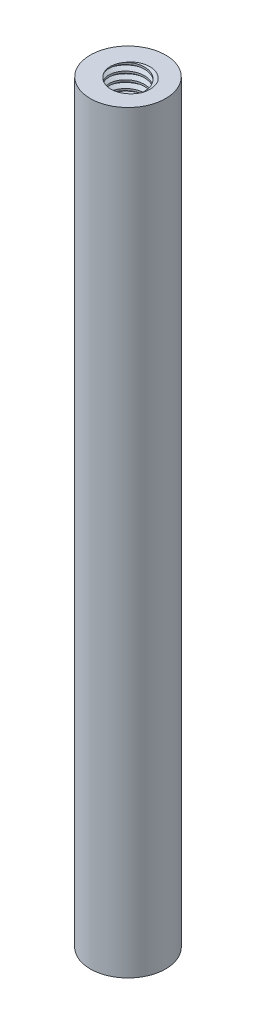
SolidWorks part; units mm, degrees
ref_plane "Front Plane" through (0, 0, 0) normal (0, 0, 1) x (1, 0, 0)
ref_plane "Top Plane" through (0, 0, 0) normal (0, 1, 0) x (1, 0, 0)
ref_plane "Right Plane" through (0, 0, 0) normal (1, 0, 0) x (0, 0, -1)
sketch "Sketch1" plane through (0, 0, 0) normal (0, 1, 0) x (1, 0, 0)
  circle A0 centre (0, 0) radius 3.5
  dimension "D1" = 7
extrude "Boss-Extrude1" add sketch "Sketch1" along normal mid plane 70
sketch "Sketch2" plane through (0, 35, 0) normal (0, 1, 0) x (1, 0, 0)
  circle A0 centre (0, 0) radius 1.65
  dimension "D1" = 3.3
extrude "Cut-Extrude1" cut sketch "Sketch2" against normal blind 6.5
thread "Thread1" pitch 0.7 method cut profile "Thread Profile1" start angle 0, offset 2, length 8, pitch 0.7, diameter 3.3
ref_plane "Plane1" through (-1.65, 37, 0) normal (0, 0, 1) x (-1, 0, 0)
sketch "Thread Profile1" plane through (-1.65, 37, 0) normal (0, 0, 1) x (-1, 0, 0)
  line L0 (0, 0) -> (0, 0.7) construction
  line L1 (0, 0) -> (0.3789, 0.2187)
  line L2 (0.3789, 0.2187) -> (0.3789, 0.3062)
  line L3 (0.3789, 0.3062) -> (0, 0.525)
  line L4 (0.3789, 0.2625) -> (0, 0.2625) construction
  line L11 (0, 0) -> (0, 0.525)
  point P2 (0, 0)
  dimension "Pitch" = 0.7
  dimension "Profile_Angle" = 60
  dimension "Profile_Land" = 0.0875
  dimension "Profile_Height" = 0.3789
mirror "Mirror3" about plane through (0, 0, 0) normal (0, 1, 0) of "Cut-Extrude1"
thread "Thread2" pitch 0.7 method cut profile "Thread Profile2" start angle 0, offset 2, length 8, pitch 0.7, diameter 3.3
ref_plane "Plane2" through (1.65, -37, 0) normal (0, 0, 1) x (1, 0, 0)
sketch "Thread Profile2" plane through (1.65, -37, 0) normal (0, 0, 1) x (1, 0, 0)
  line L0 (0, 0) -> (0, 0.7) construction
  line L1 (0, 0) -> (0.3789, 0.2187)
  line L2 (0.3789, 0.2187) -> (0.3789, 0.3062)
  line L3 (0.3789, 0.3062) -> (0, 0.525)
  line L4 (0.3789, 0.2625) -> (0, 0.2625) construction
  line L11 (0, 0) -> (0, 0.525)
  point P2 (0, 0)
  dimension "Pitch" = 0.7
  dimension "Profile_Angle" = 60
  dimension "Profile_Land" = 0.0875
  dimension "Profile_Height" = 0.3789
